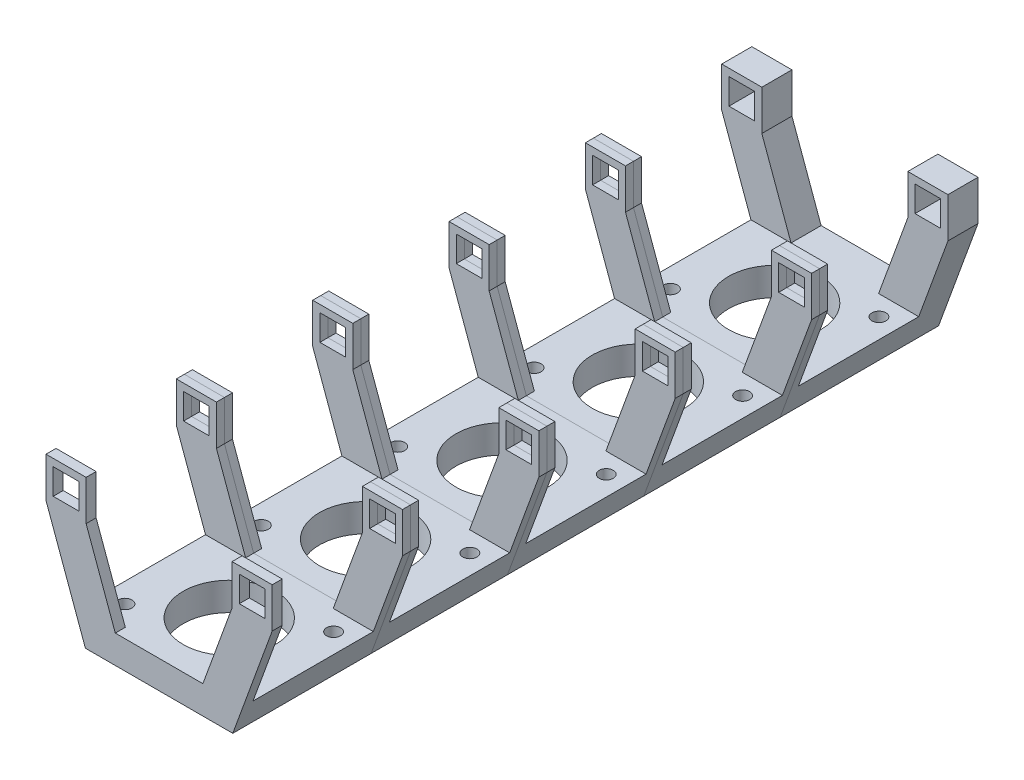
SolidWorks part; units mm, degrees
note: The reader was unsure of these and kept them because the rebuilt part matched: shared geometry of "Sketch3<4>".
ref_plane "Front Plane" through (0, 0, 0) normal (0, 0, 1) x (1, 0, 0)
ref_plane "Top Plane" through (0, 0, 0) normal (0, 1, 0) x (1, 0, 0)
ref_plane "Right Plane" through (0, 0, 0) normal (1, 0, 0) x (0, 0, -1)
sketch "Sketch3" plane through (0, 0, 0) normal (0, 0, 1) x (1, 0, 0)
  line L0 (0, 0) -> (46.4, 0) construction
  line L1 (-3.2, -3.2) -> (3.2, -3.2)
  line L2 (-3.2, -3.2) -> (-3.2, 3.2)
  line L3 (-3.2, 3.2) -> (3.2, 3.2)
  line L4 (3.2, -3.2) -> (3.2, 3.2)
  line L5 (-3.2, -3.2) -> (3.2, 3.2) construction
  line L6 (-3.2, 3.2) -> (3.2, -3.2) construction
  line L7 (43.2, -3.2) -> (49.6, -3.2)
  line L8 (43.2, -3.2) -> (43.2, 3.2)
  line L9 (43.2, 3.2) -> (49.6, 3.2)
  line L10 (49.6, -3.2) -> (49.6, 3.2)
  line L11 (43.2, -3.2) -> (49.6, 3.2) construction
  line L12 (43.2, 3.2) -> (49.6, -3.2) construction
  line L13 (-5, 5) -> (5, 5)
  line L14 (5, -5) -> (5, 5)
  line L16 (-5, -5) -> (-5, 5)
  line L18 (51.4, -5) -> (51.4, 5)
  line L19 (41.4, 5) -> (51.4, 5)
  line L20 (41.4, -5) -> (41.4, 5)
  line L21 (-5, -5) -> (-5, -25) construction
  line L22 (-5, -25) -> (51.4, -25) construction
  line L23 (51.4, -25) -> (51.4, -5) construction
  line L24 (23.2, 0) -> (23.2, 5) construction
  line L25 (23.2, 5) -> (8.2, 5) construction
  line L26 (23.2, 5) -> (38.2, 5) construction
  line L27 (8.2, 5) -> (8.2, -25) construction
  line L28 (38.2, 5) -> (38.2, -25) construction
  line L29 (-5, -5) -> (4.8272, -32)
  line L30 (4.8272, -32) -> (41.5728, -32)
  line L31 (41.5728, -32) -> (51.4, -5)
  line L32 (5, -5) -> (12.2794, -25)
  line L33 (12.2794, -25) -> (34.1206, -25)
  line L34 (34.1206, -25) -> (41.4, -5)
  line L35 (2.2794, -25) -> (12.2794, -25)
  line L36 (-5, -5) -> (5, -5) construction
  line L37 (41.4, -5) -> (51.4, -5) construction
  line L38 (34.1206, -25) -> (44.1206, -25)
  point P0 (0, 0)
  point P6 (46.4, 0)
  point P27 (2.2794, -25)
  point P34 (44.1206, -25)
  dimension "D1" = 40
  dimension "D2" = 6.4
  dimension "D4" = 30
  dimension "D5" = 30
  dimension "D6" = 7
  dimension "D7" = 20
  dimension "D8" = 20
  dimension "D9" = 20
  dimension "D10" = 20
  dimension "D3" = 1.8
extrude "Boss-Extrude1" add sketch "Sketch3" along normal blind 2 contours L29 L35 L32 L14 L13 L16 L4 L1 L2 L3 | L34 L38 L31 L18 L19 L20 L10 L7 L8 L9 | L38 L33 L35 L29 L30 L31
extrude "Boss-Extrude2" add sketch "Sketch3<4>" against normal blind 30 contours L38 L33 L35 L29 L30 L31
sketch "Sketch3<4>" plane through (0, 0, 0) normal (0, 0, 1) x (1, 0, 0) same geometry as "Sketch3"
sketch "Sketch4" plane through (0, 0, -30) normal (0, 0, -1) x (-1, 0, 0)
  line L0 (5, -5) -> (5, 5) construction
  line L1 (5, 5) -> (-5, 5) construction
  line L2 (-5, -5) -> (-5, 5) construction
  line L3 (-5, -5) -> (-12.2794, -25) construction
  line L4 (5, -5) -> (-2.2794, -25) construction
  line L5 (-2.2794, -25) -> (-4.8272, -32) construction
  line L6 (-41.5728, -32) -> (-44.1206, -25) construction
  line L7 (-4.8272, -32) -> (-41.5728, -32) construction
  line L8 (-2.2794, -25) -> (-44.1206, -25) construction
  line L9 (-34.1206, -25) -> (-41.4, -5) construction
  line L10 (-41.4, -5) -> (-41.4, 5) construction
  line L11 (-44.1206, -25) -> (-51.4, -5) construction
  line L12 (-51.4, -5) -> (-51.4, 5) construction
  line L13 (-41.4, 5) -> (-51.4, 5) construction
  line L14 (5, -5) -> (5, 5)
  line L15 (5, 5) -> (-5, 5)
  line L16 (-5, -5) -> (-5, 5)
  line L17 (-5, -5) -> (-12.2794, -25)
  line L18 (5, -5) -> (-2.2794, -25)
  line L19 (-2.2794, -25) -> (-4.8272, -32)
  line L20 (-41.5728, -32) -> (-44.1206, -25)
  line L21 (-4.8272, -32) -> (-41.5728, -32)
  line L22 (-12.2794, -25) -> (-34.1206, -25)
  line L23 (-34.1206, -25) -> (-41.4, -5)
  line L24 (-41.4, -5) -> (-41.4, 5)
  line L25 (-44.1206, -25) -> (-51.4, -5)
  line L26 (-51.4, -5) -> (-51.4, 5)
  line L27 (-41.4, 5) -> (-51.4, 5)
  line L28 (-3.2, -3.2) -> (-3.2, 3.2) construction
  line L29 (3.2, 3.2) -> (-3.2, 3.2) construction
  line L30 (3.2, -3.2) -> (3.2, 3.2) construction
  line L31 (3.2, -3.2) -> (-3.2, -3.2) construction
  line L32 (-43.2, -3.2) -> (-49.6, -3.2) construction
  line L33 (-49.6, -3.2) -> (-49.6, 3.2) construction
  line L34 (-43.2, 3.2) -> (-49.6, 3.2) construction
  line L35 (-43.2, -3.2) -> (-43.2, 3.2) construction
  line L36 (-3.2, -3.2) -> (-3.2, 3.2)
  line L37 (3.2, 3.2) -> (-3.2, 3.2)
  line L38 (3.2, -3.2) -> (3.2, 3.2)
  line L39 (3.2, -3.2) -> (-3.2, -3.2)
  line L40 (-43.2, -3.2) -> (-49.6, -3.2)
  line L41 (-49.6, -3.2) -> (-49.6, 3.2)
  line L42 (-43.2, 3.2) -> (-49.6, 3.2)
  line L43 (-43.2, -3.2) -> (-43.2, 3.2)
extrude "Boss-Extrude6" add sketch "Sketch4" along normal blind 2
pattern_linear "LPattern7" count 5 spacing 34 along (0, 0, 1) of bodies 128
sketch "Sketch12" plane through (0, 0, -32) normal (0, 0, -1) x (-1, 0, 0)
  line L0 (-5, 5) -> (-5, -5) construction
  line L1 (5, 5) -> (-5, 5) construction
  line L2 (5, -5) -> (5, 5) construction
  line L3 (3.2, -3.2) -> (3.2, 3.2) construction
  line L4 (3.2, 3.2) -> (-3.2, 3.2) construction
  line L5 (-3.2, 3.2) -> (-3.2, -3.2) construction
  line L6 (-3.2, -3.2) -> (3.2, -3.2) construction
  line L7 (-5, -5) -> (-12.2794, -25) construction
  line L8 (-4.8272, -32) -> (5, -5) construction
  line L9 (-12.2794, -25) -> (-34.1206, -25) construction
  line L10 (-41.5728, -32) -> (-4.8272, -32) construction
  line L11 (-41.4, -5) -> (-41.4, 5) construction
  line L12 (-34.1206, -25) -> (-41.4, -5) construction
  line L13 (-51.4, -5) -> (-41.5728, -32) construction
  line L14 (-49.6, -3.2) -> (-43.2, -3.2) construction
  line L15 (-43.2, -3.2) -> (-43.2, 3.2) construction
  line L16 (-43.2, 3.2) -> (-49.6, 3.2) construction
  line L17 (-49.6, 3.2) -> (-49.6, -3.2) construction
  line L18 (-51.4, 5) -> (-51.4, -5) construction
  line L19 (-41.4, 5) -> (-51.4, 5) construction
  line L20 (-5, 5) -> (-5, -5)
  line L21 (5, 5) -> (-5, 5)
  line L22 (5, -5) -> (5, 5)
  line L23 (3.2, -3.2) -> (3.2, 3.2)
  line L24 (3.2, 3.2) -> (-3.2, 3.2)
  line L25 (-3.2, 3.2) -> (-3.2, -3.2)
  line L26 (-3.2, -3.2) -> (3.2, -3.2)
  line L27 (-5, -5) -> (-12.2794, -25)
  line L28 (-4.8272, -32) -> (5, -5)
  line L29 (-12.2794, -25) -> (-34.1206, -25)
  line L30 (-41.5728, -32) -> (-4.8272, -32)
  line L31 (-41.4, -5) -> (-41.4, 5)
  line L32 (-34.1206, -25) -> (-41.4, -5)
  line L33 (-51.4, -5) -> (-41.5728, -32)
  line L34 (-49.6, -3.2) -> (-43.2, -3.2)
  line L35 (-43.2, -3.2) -> (-43.2, 3.2)
  line L36 (-43.2, 3.2) -> (-49.6, 3.2)
  line L37 (-49.6, 3.2) -> (-49.6, -3.2)
  line L38 (-51.4, 5) -> (-51.4, -5)
  line L39 (-41.4, 5) -> (-51.4, 5)
extrude "Boss-Extrude7" add sketch "Sketch12" along normal blind 2
sketch "Sketch13" plane through (0, 0, 138) normal (0, 0, 1) x (1, 0, 0)
  line L0 (43.2, -3.2) -> (43.2, 3.2) construction
  line L1 (41.4, -5) -> (41.4, 5) construction
  line L2 (43.2, 3.2) -> (49.6, 3.2) construction
  line L3 (41.4, 5) -> (51.4, 5) construction
  line L4 (51.4, -5) -> (51.4, 5) construction
  line L5 (49.6, -3.2) -> (49.6, 3.2) construction
  line L6 (43.2, -3.2) -> (49.6, -3.2) construction
  line L7 (41.5728, -32) -> (51.4, -5) construction
  line L8 (34.1206, -25) -> (41.4, -5) construction
  line L9 (4.8272, -32) -> (41.5728, -32) construction
  line L10 (12.2794, -25) -> (34.1206, -25) construction
  line L11 (5, -5) -> (12.2794, -25) construction
  line L12 (-5, -5) -> (4.8272, -32) construction
  line L13 (5, -5) -> (5, 5) construction
  line L14 (-3.2, -3.2) -> (3.2, -3.2) construction
  line L15 (3.2, -3.2) -> (3.2, 3.2) construction
  line L16 (-3.2, -3.2) -> (-3.2, 3.2) construction
  line L17 (-3.2, 3.2) -> (3.2, 3.2) construction
  line L18 (-5, -5) -> (-5, 5) construction
  line L19 (-5, 5) -> (5, 5) construction
  line L20 (43.2, -3.2) -> (43.2, 3.2)
  line L21 (41.4, -5) -> (41.4, 5)
  line L22 (43.2, 3.2) -> (49.6, 3.2)
  line L23 (41.4, 5) -> (51.4, 5)
  line L24 (51.4, -5) -> (51.4, 5)
  line L25 (49.6, -3.2) -> (49.6, 3.2)
  line L26 (43.2, -3.2) -> (49.6, -3.2)
  line L27 (41.5728, -32) -> (51.4, -5)
  line L28 (34.1206, -25) -> (41.4, -5)
  line L29 (4.8272, -32) -> (41.5728, -32)
  line L30 (12.2794, -25) -> (34.1206, -25)
  line L31 (5, -5) -> (12.2794, -25)
  line L32 (-5, -5) -> (4.8272, -32)
  line L33 (5, -5) -> (5, 5)
  line L34 (-3.2, -3.2) -> (3.2, -3.2)
  line L35 (3.2, -3.2) -> (3.2, 3.2)
  line L36 (-3.2, -3.2) -> (-3.2, 3.2)
  line L37 (-3.2, 3.2) -> (3.2, 3.2)
  line L38 (-5, -5) -> (-5, 5)
  line L39 (-5, 5) -> (5, 5)
extrude "Boss-Extrude8" add sketch "Sketch13" along normal blind 2
sketch "Sketch15" plane through (0, -25, 0) normal (0, 1, 0) x (1, 0, 0)
  line L0 (23.2, -104) -> (23.2, -140) construction
  line L1 (12.2794, -104) -> (34.1206, -104) construction
  line L2 (34.1206, -140) -> (12.2794, -140) construction
  line L3 (2.2794, -121) -> (44.1206, -121) construction
  line L4 (2.2794, -106) -> (2.2794, -136) construction
  line L5 (44.1206, -106) -> (44.1206, -136) construction
  line L6 (7.2, -131) -> (23.2, -131) construction
  line L7 (7.2, -131) -> (7.2, -121) construction
  circle A0 centre (23.2, -121) radius 11.5
  circle A1 centre (23.2, -121) radius 16 construction
  circle A2 centre (7.2, -131) radius 1.75
  circle A3 centre (39.2, -111) radius 1.75
  dimension "D1" = 23
  dimension "D2" = 32
  dimension "D3" = 3.5
  dimension "D4" = 10
  dimension "D5" = 16
  dimension "D6" = 16
  dimension "D7" = 10
extrude "Cut-Extrude5" cut sketch "Sketch15" against normal up to surface (7 mm away)
pattern_linear "LPattern8" count 5 spacing 34 along (0, 0, -1) of "Cut-Extrude5"
sketch "Sketch17" plane through (0, 0, 140) normal (0, 0, 1) x (1, 0, 0)
  line L0 (-5, 5) -> (5, 5)
  line L1 (5, 5) -> (5, -5)
  line L2 (5, -5) -> (12.2794, -25)
  line L3 (12.2794, -25) -> (34.1206, -25)
  line L4 (34.1206, -25) -> (41.4, -5)
  line L5 (41.4, -5) -> (41.4, 5)
  line L6 (41.4, 5) -> (51.4, 5)
  line L7 (51.4, 5) -> (51.4, -5)
  line L8 (51.4, -5) -> (41.5728, -32)
  line L9 (41.5728, -32) -> (4.8272, -32)
  line L10 (4.8272, -32) -> (-5, -5)
  line L11 (-5, -5) -> (-5, 5)
extrude "Cut-Extrude6" cut sketch "Sketch17" against normal blind 1.5
sketch "Sketch18" plane through (0, 0, -34) normal (0, 0, -1) x (-1, 0, 0)
  line L0 (5, -5) -> (5, 5) construction
  line L1 (5, 5) -> (-5, 5) construction
  line L2 (-5, 5) -> (-5, -5) construction
  line L3 (-3.2, 3.2) -> (-3.2, -3.2) construction
  line L4 (3.2, 3.2) -> (-3.2, 3.2) construction
  line L5 (3.2, -3.2) -> (3.2, 3.2) construction
  line L6 (-3.2, -3.2) -> (3.2, -3.2) construction
  line L7 (-4.8272, -32) -> (5, -5) construction
  line L8 (-5, -5) -> (-12.2794, -25) construction
  line L9 (-41.5728, -32) -> (-4.8272, -32) construction
  line L10 (-12.2794, -25) -> (-34.1206, -25) construction
  line L11 (-34.1206, -25) -> (-41.4, -5) construction
  line L12 (-51.4, -5) -> (-41.5728, -32) construction
  line L13 (-51.4, 5) -> (-51.4, -5) construction
  line L14 (-49.6, -3.2) -> (-43.2, -3.2) construction
  line L15 (-49.6, 3.2) -> (-49.6, -3.2) construction
  line L16 (-43.2, -3.2) -> (-43.2, 3.2) construction
  line L17 (-43.2, 3.2) -> (-49.6, 3.2) construction
  line L18 (-41.4, -5) -> (-41.4, 5) construction
  line L19 (-41.4, 5) -> (-51.4, 5) construction
  line L20 (5, -5) -> (5, 5)
  line L21 (5, 5) -> (-5, 5)
  line L22 (-5, 5) -> (-5, -5)
  line L23 (-3.2, 3.2) -> (-3.2, -3.2)
  line L24 (3.2, 3.2) -> (-3.2, 3.2)
  line L25 (3.2, -3.2) -> (3.2, 3.2)
  line L26 (-3.2, -3.2) -> (3.2, -3.2)
  line L27 (-4.8272, -32) -> (5, -5)
  line L28 (-5, -5) -> (-12.2794, -25)
  line L29 (-41.5728, -32) -> (-4.8272, -32)
  line L30 (-12.2794, -25) -> (-34.1206, -25)
  line L31 (-34.1206, -25) -> (-41.4, -5)
  line L32 (-51.4, -5) -> (-41.5728, -32)
  line L33 (-51.4, 5) -> (-51.4, -5)
  line L34 (-49.6, -3.2) -> (-43.2, -3.2)
  line L35 (-49.6, 3.2) -> (-49.6, -3.2)
  line L36 (-43.2, -3.2) -> (-43.2, 3.2)
  line L37 (-43.2, 3.2) -> (-49.6, 3.2)
  line L38 (-41.4, -5) -> (-41.4, 5)
  line L39 (-41.4, 5) -> (-51.4, 5)
extrude "Boss-Extrude9" add sketch "Sketch18" along normal blind 3.5
